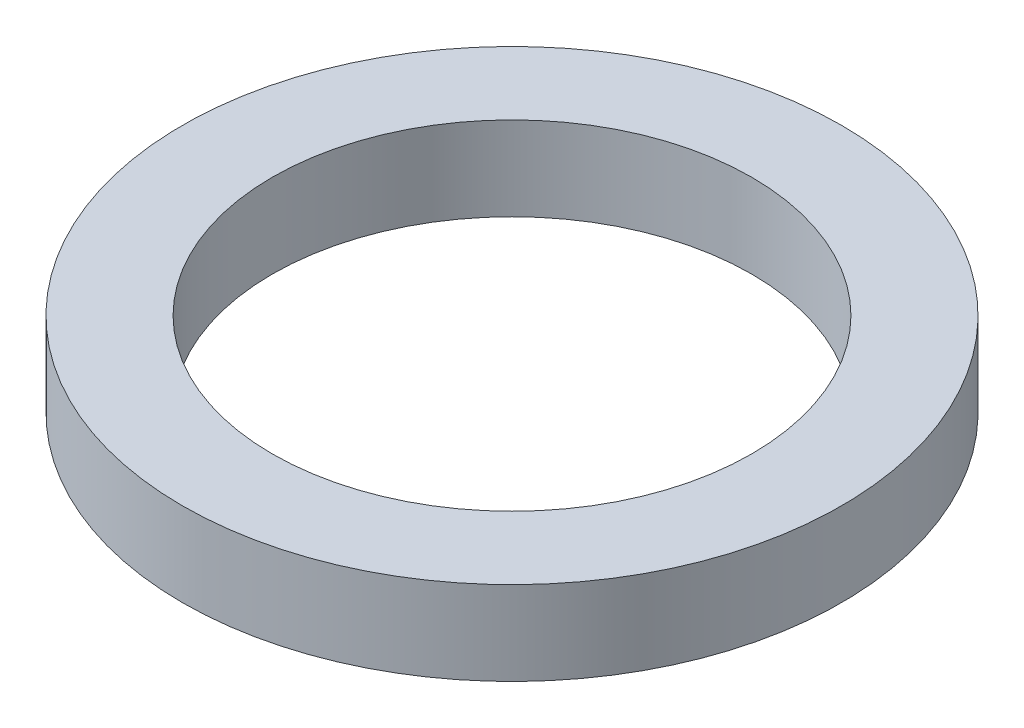
SolidWorks part; units mm, degrees
ref_plane "Front Plane" through (0, 0, 0) normal (0, 0, 1) x (1, 0, 0)
ref_plane "Top Plane" through (0, 0, 0) normal (0, 1, 0) x (1, 0, 0)
ref_plane "Right Plane" through (0, 0, 0) normal (1, 0, 0) x (0, 0, -1)
sketch "Sketch1" plane through (0, 0, 0) normal (0, 1, 0) x (1, 0, 0)
  circle A0 centre (0, 0) radius 55
  dimension "FLANGE_OD" = 110
extrude "Boss-Extrude1" add sketch "Sketch1" along normal blind 14
sketch "Sketch2" plane through (0, 0, 0) normal (0, 1, 0) x (1, 0, 0)
  circle A0 centre (0, 0) radius 40
  dimension "BORE_D" = 80
extrude "Cut-Extrude1" cut sketch "Sketch2" along normal through all
sketch "Sketch3" plane through (0, 14, 0) normal (0, 1, 0) x (1, 0, 0)
  circle A0 centre (0, 0) radius 23.0344 construction
  circle A1 centre (-23.0344, 0) radius 2.0765
  dimension "BOLT_D" = 4.153
  dimension "BOLT_PCD" = 46.0689
extrude "Cut-Extrude2" cut sketch "Sketch3" against normal blind 10.82 rebuild error yes
pattern_circular "CirPattern1" count 6 over 360 rebuild error yes
